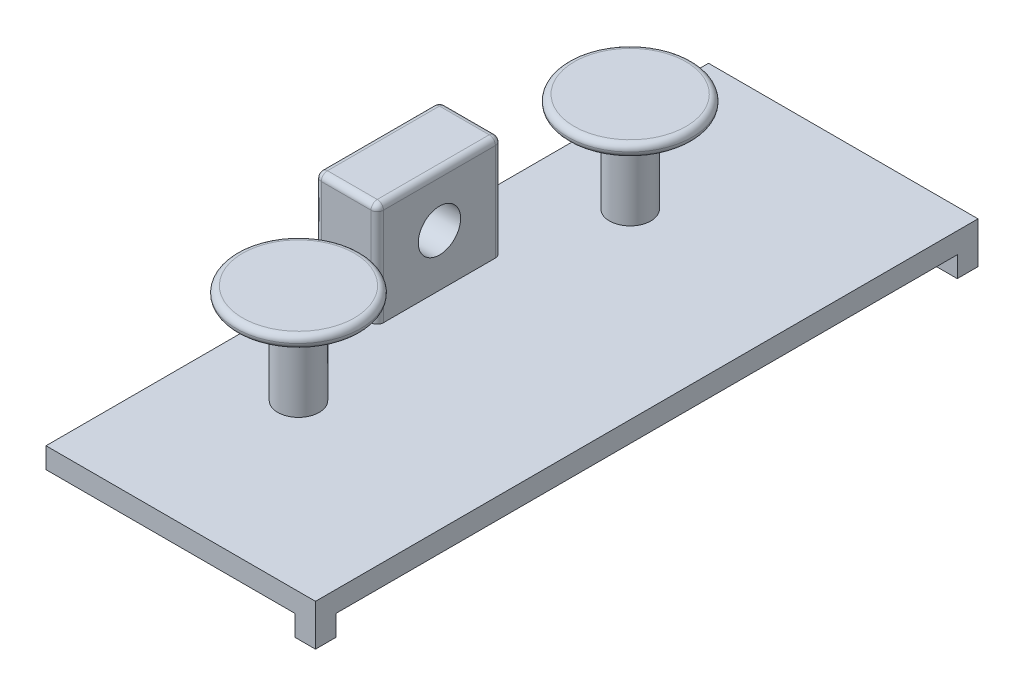
SolidWorks part; units mm, degrees
ref_plane "Ebene vorne" through (0, 0, 0) normal (0, 0, 1) x (1, 0, 0)
ref_plane "Ebene oben" through (0, 0, 0) normal (0, 1, 0) x (1, 0, 0)
ref_plane "Ebene rechts" through (0, 0, 0) normal (1, 0, 0) x (0, 0, -1)
sketch "Sketch1" plane through (0, 0, 0) normal (0, 1, 0) x (1, 0, 0)
  line L1 (-32.5, 79.9) -> (32.5, 79.9)
  line L2 (-32.5, 79.9) -> (-32.5, -79.9)
  line L3 (-32.5, -79.9) -> (32.5, -79.9)
  line L4 (32.5, 79.9) -> (32.5, -79.9)
  line L5 (-32.5, 79.9) -> (32.5, -79.9) construction
  line L6 (-32.5, -79.9) -> (32.5, 79.9) construction
  point P1 (0, 0)
  dimension "D1" = 159.8
  dimension "D2" = 65
extrude "Boss-Extrude1" add sketch "Sketch1" along normal mid plane 5
sketch "Sketch2" plane through (0, 2.5, 0) normal (0, 1, 0) x (1, 0, 0)
  line L5 (-7.5, 0) -> (25.6568, 0) construction
  line L6 (-32.5, 79.9) -> (-32.5, -79.9) construction
  line L10 (-17.5, 15) -> (-32.5, 15)
  line L11 (-17.5, 15) -> (-17.5, -15)
  line L12 (-17.5, -15) -> (-32.5, -15)
  line L20 (-32.5, 15) -> (-32.5, -15)
  line L21 (-17.5, 15) -> (-32.5, -15) construction
  line L22 (-17.5, -15) -> (-32.5, 15) construction
  point P0 (-25, 0)
  dimension "D1" = 30
  dimension "D2" = 15
extrude "Boss-Extrude2" add sketch "Sketch2" along normal blind 25
sketch "Sketch3" plane through (-32.5, 0, 0) normal (-1, 0, 0) x (0, 0, 1)
  line L2 (-15, 15) -> (15, 15) construction
  line L3 (-15, 27.5) -> (-15, 2.5) construction
  line L4 (15, 27.5) -> (15, 2.5) construction
  line L5 (-79.9, -2.5) -> (79.9, -2.5) construction
  line L6 (-15, 27.5) -> (15, 27.5) construction
  circle A0 centre (0, 15) radius 5.1
  dimension "D1" = 10.2
  dimension "D3" = 12.5
  dimension "D2" = 17.5
extrude "Cut-Extrude1" cut sketch "Sketch3" against normal through all
sketch "Sketch6" plane through (0, -2.5, 0) normal (0, -1, 0) x (1, 0, 0)
  line L1 (32.5, 79.9) -> (27.5, 79.9)
  line L2 (32.5, 79.9) -> (32.5, 74.9)
  line L3 (32.5, 74.9) -> (27.5, 74.9)
  line L4 (27.5, 79.9) -> (27.5, 74.9)
  line L5 (32.5, -79.9) -> (27.5, -79.9)
  line L6 (32.5, -79.9) -> (32.5, -74.9)
  line L7 (32.5, -74.9) -> (27.5, -74.9)
  line L8 (27.5, -79.9) -> (27.5, -74.9)
  dimension "D1" = 5
extrude "Boss-Extrude4" add sketch "Sketch6" along normal blind 5
sketch "Sketch7" plane through (0, 2.5, 0) normal (0, 1, 0) x (1, 0, 0)
  line L0 (32.5, 0) -> (-32.5, 0) construction
  line L4 (-17.5, -15) -> (-17.5, 15) construction
  line L5 (32.5, -79.9) -> (32.5, 79.9) construction
  line L6 (-32.5, 15) -> (-32.5, -15) construction
  circle A0 centre (-11.5, 40) radius 5
  circle A1 centre (-11.5, -40) radius 5
  dimension "D1" = 10
  dimension "D2" = 40
  dimension "D3" = 6
extrude "Boss-Extrude5" add sketch "Sketch7" along normal blind 21
sketch "Sketch8" plane through (0, 23.5, 0) normal (0, 1, 0) x (1, 0, 0)
  line L0 (-19.25, 0) -> (19.25, 0) construction
  circle A0 centre (-11.5, 40) radius 15
  circle A1 centre (-11.5, -40) radius 15
  dimension "D1" = 30
extrude "Boss-Extrude6" add sketch "Sketch8" along normal blind 3
fillet "Fillet1" radius 1.5 4 edges at (-11.5, 23.5, 25) (-11.5, 26.5, 25) (-11.5, 23.5, -25) (-11.5, 26.5, -25)
chamfer "Chamfer1" distance 1.5 angle 45 1 edges at (-32.5, 15, 5.1)
fillet "Fillet2" radius 1.5 8 edges at (-17.5, 15, -15) (-17.5, 15, 15) (-25, 27.5, 15) (-17.5, 27.5, 0) (-32.5, 27.5, 0) (-25, 27.5, -15) (-32.5, 15, -15) (-32.5, 15, 15)
